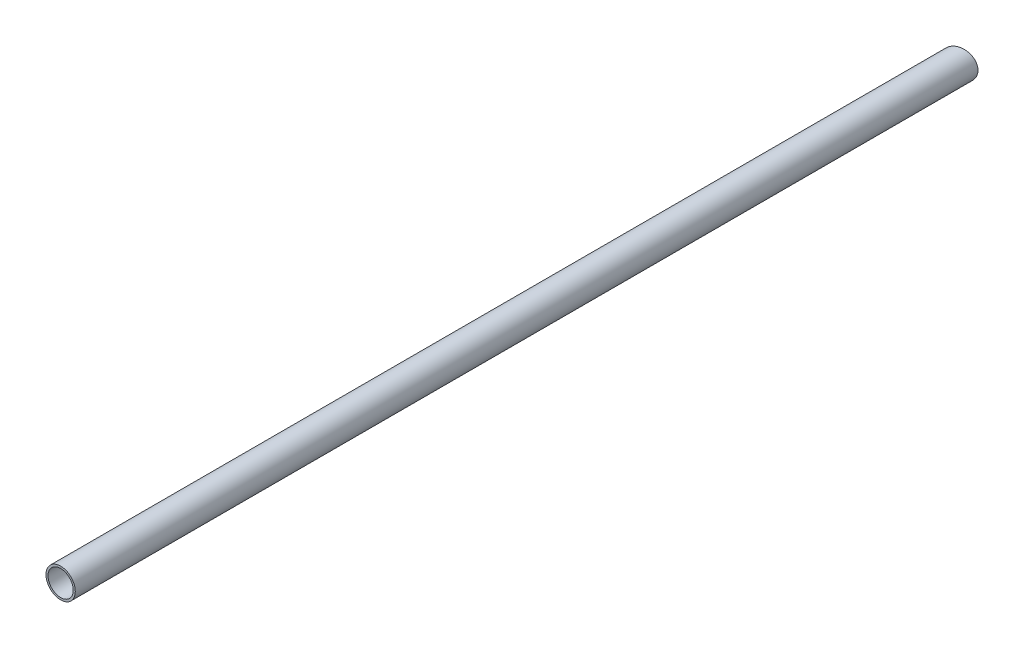
SolidWorks part; units mm, degrees
material "1060 Alloy"
ref_plane "Front Plane" through (0, 0, 0) normal (0, 0, 1) x (1, 0, 0)
ref_plane "Top Plane" through (0, 0, 0) normal (0, 1, 0) x (1, 0, 0)
ref_plane "Right Plane" through (0, 0, 0) normal (1, 0, 0) x (0, 0, -1)
sketch "Sketch1" plane through (0, 0, 0) normal (0, 0, 1) x (1, 0, 0)
  circle A0 centre (0, 0) radius 12.7
  circle A1 centre (0, 0) radius 10.922
  dimension "D1" = 25.4
  dimension "D2" = 1.778
extrude "Boss-Extrude1" add sketch "Sketch1" along normal blind 782.32
ref_axis "Axis1" through (0, 0, 782.32) along (0, 0, -1)
sketch "Sketch3" plane through (0, 0, 0) normal (0, 1, 0) x (1, 0, 0)
  line L0 (0, 0) -> (12.7, 0)
  line L1 (12.7, 0) -> (-50.8, -17.0148)
  line L2 (12.7, -782.32) -> (12.7, 0) construction
  line L3 (0, 0) -> (-50.8, 0)
  line L4 (-50.8, 0) -> (-50.8, -17.0148)
  dimension "D1" = 15
  dimension "D2" = 63.5
extrude "Cut-Extrude1" cut sketch "Sketch3" against normal through all both and the other way through all
